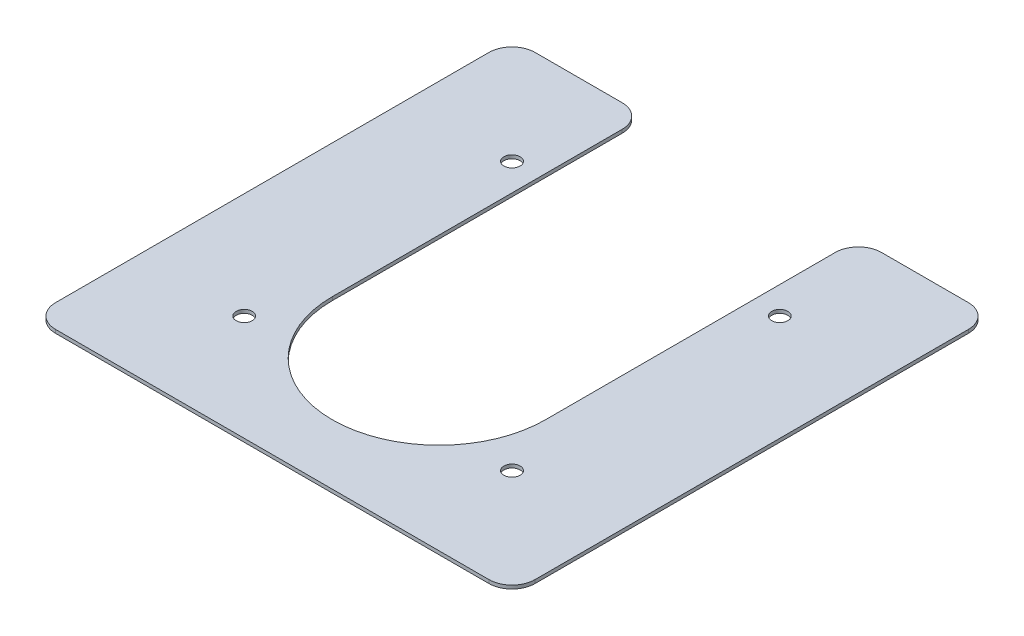
SolidWorks part; units mm, degrees
ref_plane "Front Plane" through (0, 0, 0) normal (0, 0, 1) x (1, 0, 0)
ref_plane "Top Plane" through (0, 0, 0) normal (0, 1, 0) x (1, 0, 0)
ref_plane "Right Plane" through (0, 0, 0) normal (1, 0, 0) x (0, 0, -1)
sketch "Sketch1" plane through (0, 0, 0) normal (0, 1, 0) x (1, 0, 0)
  line L0 (0, 0) -> (0, 21) construction
  line L1 (51.8722, -39.9014) -> (51.8722, 63.843) construction
  line L3 (51.8722, 63.843) -> (-51.8722, 63.843) construction
  line L4 (-51.8722, 63.843) -> (-51.8722, -39.9014) construction
  line L5 (51.8722, -34.9014) -> (51.8722, 58.843)
  line L6 (-46.8722, -39.9014) -> (46.8722, -39.9014)
  line L7 (51.8722, 63.843) -> (-51.8722, 63.843) construction
  line L8 (-51.8722, 58.843) -> (-51.8722, -34.9014)
  line L10 (36.8722, -39.9014) -> (36.8722, 63.843) construction
  line L11 (-36.8722, -39.9014) -> (-36.8722, 63.843) construction
  line L12 (36.8722, -39.9014) -> (36.8722, 63.843) construction
  line L13 (-36.8722, -39.9014) -> (-36.8722, 63.843) construction
  line L14 (23.0585, -3.843) -> (23.0585, 58.843)
  line L15 (-23.0585, -3.843) -> (-23.0585, 58.843)
  line L16 (-46.8722, 63.843) -> (-28.0585, 63.843)
  line L17 (28.0585, 63.843) -> (46.8722, 63.843)
  circle A0 centre (0, 0) radius 21 construction
  circle A1 centre (0, 0) radius 21 construction
  circle A2 centre (28.9653, -16.9946) radius 1.75 construction
  circle A3 centre (-28.9653, -16.9946) radius 1.75 construction
  circle A4 centre (28.9653, 40.9361) radius 1.75 construction
  circle A5 centre (-28.9653, 40.9361) radius 1.75 construction
  circle A6 centre (28.9653, -16.9946) radius 1.75
  circle A7 centre (-28.9653, -16.9946) radius 1.75
  circle A8 centre (28.9653, 40.9361) radius 1.75
  circle A9 centre (-28.9653, 40.9361) radius 1.75
  circle A10 centre (0, -3.843) radius 21.0585 construction
  arc A11 (-21.0585, -3.843) -> (21.0585, -3.843) centre (0, -3.843) ccw construction
  arc A12 (-23.0585, -3.843) -> (23.0585, -3.843) centre (0, -3.843) ccw
  arc A13 (28.0585, 63.843) -> (23.0585, 58.843) centre (28.0585, 58.843) ccw
  circle A14 centre (0, -3.843) radius 23.0585 construction
  arc A15 (-28.0585, 63.843) -> (-23.0585, 58.843) centre (-28.0585, 58.843) cw
  arc A16 (46.8722, 63.843) -> (51.8722, 58.843) centre (46.8722, 58.843) cw
  arc A17 (51.8722, -34.9014) -> (46.8722, -39.9014) centre (46.8722, -34.9014) cw
  arc A18 (-46.8722, -39.9014) -> (-51.8722, -34.9014) centre (-46.8722, -34.9014) cw
  arc A19 (-51.8722, 58.843) -> (-46.8722, 63.843) centre (-46.8722, 58.843) cw
  point P39 (31.0585, -3.843)
  point P42 (23.0585, 63.843)
  point P45 (-23.0585, 63.843)
  dimension "D1" = 2
  dimension "D2" = 5
sketch "Sketch2" plane through (0, 0, 0) normal (0, 0, 1) x (1, 0, 0)
  line L1 (51.8722, -0.75) -> (-51.8722, -0.75)
  line L2 (51.8722, -0.75) -> (51.8722, 0)
  line L3 (51.8722, 0) -> (-51.8722, 0)
  line L4 (-51.8722, -0.75) -> (-51.8722, 0)
extrude "Boss-Extrude1" add sketch "Sketch1" against normal up to vertex (0.75 mm away) up to point (51.8722, -0.75, 0)
